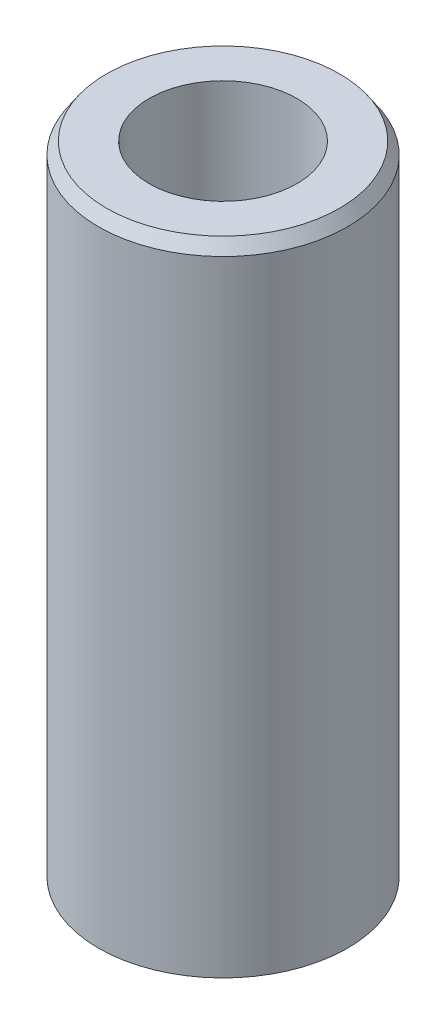
SolidWorks part; units mm, degrees
ref_plane "Front Plane" through (0, 0, 0) normal (0, 0, 1) x (1, 0, 0)
ref_plane "Top Plane" through (0, 0, 0) normal (0, 1, 0) x (1, 0, 0)
ref_plane "Right Plane" through (0, 0, 0) normal (1, 0, 0) x (0, 0, -1)
sketch "Sketch1" plane through (0, 0, 0) normal (0, 1, 0) x (1, 0, 0)
  circle A0 centre (0, 0) radius 32.5
  dimension "SHAFT_OD" = 65
extrude "Boss-Extrude1" add sketch "Sketch1" along normal blind 168.2365
sketch "Sketch2" plane through (0, 0, 0) normal (0, 1, 0) x (1, 0, 0)
  circle A0 centre (0, 0) radius 19.274
  dimension "BORE_D" = 38.548
extrude "Cut-Extrude1" cut sketch "Sketch2" along normal through all
chamfer "Chamfer1" distance 3.1247 angle 33.986 2 edges at (0, 168.2365, 32.5) (0, 0, 32.5) first distance on face at (0, 168.2365, 32.5) first distance on face at (0, 0, 19.274)
